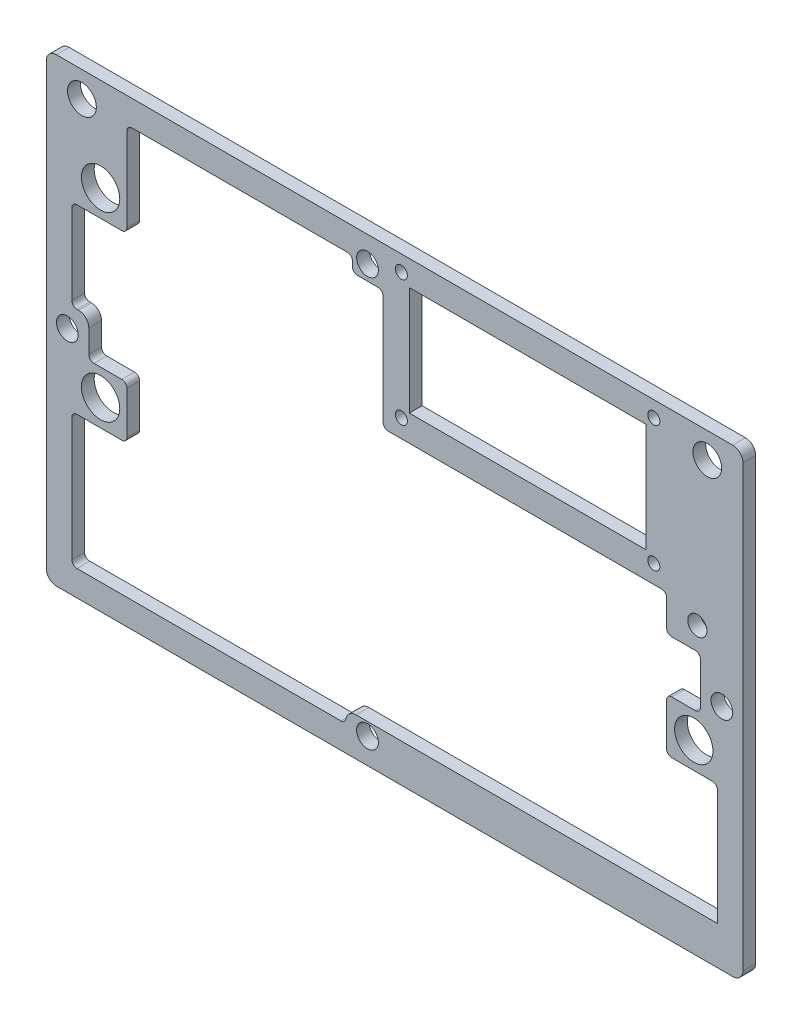
SolidWorks part; units mm, degrees
material "ABS PC"
ref_plane "Front Plane" through (0, 0, 0) normal (0, 0, 1) x (1, 0, 0)
ref_plane "Top Plane" through (0, 0, 0) normal (0, 1, 0) x (1, 0, 0)
ref_plane "Right Plane" through (0, 0, 0) normal (1, 0, 0) x (0, 0, -1)
sketch "Sketch1" plane through (0, 0, 0) normal (0, 0, 1) x (1, 0, 0)
  line L0 (94.968, 16.637) -> (-44.732, 16.637) construction
  line L1 (-61.4007, -97.663) -> (111.6368, -97.663)
  line L2 (-61.4007, -97.663) -> (-61.4007, 16.637)
  line L3 (-61.4007, 16.637) -> (111.6368, 16.637)
  line L4 (111.6368, -97.663) -> (111.6368, 16.637)
  line L5 (-61.4007, -97.663) -> (111.6368, 16.637) construction
  line L6 (-61.4007, 16.637) -> (111.6368, -97.663) construction
  point P4 (25.118, -40.513)
extrude "Boss-Extrude1" add sketch "Sketch1" along normal blind 3.175
sketch "Sketch3" plane through (0, 0, 3.175) normal (0, 0, 1) x (1, 0, 0)
  circle A0 centre (100.302, -26.543) radius 2.3813
  circle A1 centre (99.413, -51.6255) radius 4.7625
  circle A2 centre (-47.907, -51.6255) radius 4.7625
  circle A3 centre (-47.907, -6.5405) radius 4.7625
  dimension "D1" = 4.7625
  dimension "D2" = 9.525
extrude "Cut-Extrude1" cut sketch "Sketch3" against normal through all
hole_wizard "#6 Clearance Hole1" positions "Sketch5" profile "Sketch4" hole size "#6" standard "ANSI Inch" end condition through all
sketch "Sketch5" plane through (0, 0, 3.175) normal (0, 0, 1) x (1, 0, 0)
  point P0 (18.387, 10.287)
  point P3 (-56.162, -40.894)
  point P6 (106.398, -40.894)
  point P9 (18.387, -91.313)
sketch "Sketch4" plane through (18.387, 10.287, 3.175) normal (1, 0, 0) x (0, -1, 0)
  line L0 (0, 0) -> (0, 3.175)
  line L1 (0, 3.175) -> (2.1526, 3.175)
  line L2 (2.1526, 3.175) -> (2.1526, 0)
  line L5 (2.1526, 0) -> (0, 0)
  line L11 (0, -6.35) -> (0, 107.95) construction
  dimension "Thru Hole Dia." = 4.3053
  dimension "Thru Hole Depth" = 3.175
hole_wizard "#2 Clearance Hole1" positions "Sketch7" profile "Sketch6" hole size "#2" standard "ANSI Inch" end condition through all
sketch "Sketch7" plane through (0, 0, 3.175) normal (0, 0, 1) x (1, 0, 0)
  point P0 (26.788, 12.7)
  point P3 (89.488, 12.7)
  point P6 (89.488, -18.6)
  point P9 (26.788, -18.6)
sketch "Sketch6" plane through (26.788, 12.7, 3.175) normal (1, 0, 0) x (0, -1, 0)
  line L0 (0, 0) -> (0, 3.175)
  line L1 (0, 3.175) -> (1.3525, 3.175)
  line L2 (1.3525, 3.175) -> (1.3525, 0)
  line L5 (1.3525, 0) -> (0, 0)
  line L11 (0, -6.35) -> (0, 107.95) construction
  dimension "Thru Hole Dia." = 2.7051
  dimension "Thru Hole Depth" = 3.175
sketch "Sketch8" plane through (0, 0, 3.175) normal (0, 0, 1) x (1, 0, 0)
  line L9 (92.658, -23.1276) -> (22.2605, -23.1276)
  line L10 (22.2605, -23.1276) -> (22.2605, 6.5468)
  line L11 (22.2605, 6.5468) -> (14.6469, 6.5468)
  line L12 (92.658, -23.1276) -> (92.658, -32.1509)
  line L13 (28.768, 10.37) -> (28.768, -16.62)
  line L14 (28.768, -16.62) -> (87.508, -16.62)
  line L15 (87.508, -16.62) -> (87.508, 10.37)
  line L16 (87.508, 10.37) -> (28.768, 10.37)
  line L17 (28.768, 10.37) -> (28.768, -16.62)
  line L18 (28.768, -16.62) -> (87.508, -16.62)
  line L19 (87.508, -16.62) -> (87.508, 10.37)
  line L20 (87.508, 10.37) -> (28.768, 10.37)
  line L21 (92.658, -32.1509) -> (101.0704, -32.1509)
  line L22 (101.0704, -32.1509) -> (101.0704, -45.0855)
  line L23 (101.0704, -45.0855) -> (92.658, -45.0855)
  line L24 (92.658, -45.0855) -> (92.658, -58.1655)
  line L25 (92.658, -58.1655) -> (105.2868, -58.1655)
  line L26 (105.2868, -58.1655) -> (105.2868, -88.138)
  line L27 (105.2868, -88.138) -> (13.0594, -88.138)
  line L28 (13.0594, -88.138) -> (13.0594, -91.313)
  line L29 (13.0594, -91.313) -> (-55.0507, -91.313)
  line L30 (-55.0507, -91.313) -> (-55.0507, -58.1655)
  line L31 (-55.0507, -58.1655) -> (-41.367, -58.1655)
  line L32 (-41.367, -58.1655) -> (-41.367, -45.0855)
  line L33 (-41.367, -45.0855) -> (-50.8343, -45.0855)
  line L34 (-50.8343, -45.0855) -> (-50.8343, -35.5664)
  line L35 (-50.8343, -35.5664) -> (-55.0507, -35.5664)
  line L36 (-55.0507, -35.5664) -> (-55.0507, -13.0805)
  line L37 (-55.0507, -13.0805) -> (-41.367, -13.0805)
  line L38 (-41.367, -13.0805) -> (-41.367, 10.287)
  line L39 (14.6469, 6.5468) -> (14.6469, 10.287)
  line L40 (14.6469, 10.287) -> (-41.367, 10.287)
  line L43 (92.658, -45.0855) -> (109.0968, -45.0855) construction
  line L44 (111.6368, -97.663) -> (111.6368, 16.637) construction
  line L45 (-61.4007, -97.663) -> (111.6368, -97.663) construction
  line L46 (-61.4007, 16.637) -> (-61.4007, -97.663) construction
  line L47 (111.6368, 16.637) -> (-61.4007, 16.637) construction
  circle A1 centre (106.398, -40.894) radius 2.1526 construction
  circle A3 centre (18.387, -91.313) radius 2.1526 construction
  circle A8 centre (-56.162, -40.894) radius 2.1526 construction
  circle A11 centre (18.387, 10.287) radius 2.1526 construction
  circle A13 centre (26.788, -18.6) radius 1.3525 construction
  dimension "D1" = 1.27
  dimension "D10" = 1.5875
  dimension "D2" = 3.175
  dimension "D3" = 6.35
  dimension "D4" = 9.525
  dimension "D5" = 3.175
  dimension "D6" = 6.35
  dimension "D7" = 6.35
  dimension "D8" = 3.175
  dimension "D9" = 3.175
  dimension "D11" = 1.5875
  dimension "D12" = 6.35
  dimension "D13" = 3.175
  dimension "D14" = 3.175
extrude "Cut-Extrude2" cut sketch "Sketch8" against normal through all contours L19 L20 L17 L18 | L39 L40 L38 L37 L36 L35 L34 L33 L32 L31 L30 L29 L28 L27 L26 L25 L24 L23 L22 L21 L12 L9 L10 L11 region at (16.8246, -47.9652, 3.175) region at (58.138, -3.125, 3.175)
hole_wizard "#3 (0.213) Diameter Hole1" positions "3DSketch1" profile "Sketch9" hole size "#3" standard "ANSI Inch" end condition through all
sketch3d "3DSketch1"
  line L0 (18.387, 10.287, 0) -> (18.387, 10.287, 3.175) construction
  line L1 (-56.162, -40.894, 0) -> (-56.162, -40.894, 3.175) construction
  line L2 (18.387, -91.313, 0) -> (18.387, -91.313, 3.175) construction
  line L3 (106.398, -40.894, 0) -> (106.398, -40.894, 3.175) construction
  point P0 (18.387, 10.287, 3.175)
  point P5 (-56.162, -40.894, 3.175)
  point P9 (18.387, -91.313, 3.175)
  point P13 (106.398, -40.894, 3.175)
sketch "Sketch9" plane through (18.387, 10.287, 3.175) normal (1, 0, 0) x (0, -1, 0)
  line L0 (0, 0) -> (0, 3.175)
  line L1 (0, 3.175) -> (2.7051, 3.175)
  line L2 (2.7051, 3.175) -> (2.7051, 0)
  line L5 (2.7051, 0) -> (0, 0)
  line L11 (0, -6.35) -> (0, 107.95) construction
  dimension "Thru Hole Dia." = 5.4102
  dimension "Thru Hole Depth" = 3.175
hole_wizard "Ø3.0 (3) Diameter Hole1" positions "Sketch11" profile "Sketch10" hole size "Ø3.0" standard "ANSI Metric" end condition through all
sketch "Sketch11" plane through (0, 0, 3.175) normal (0, 0, 1) x (1, 0, 0)
  point P0 (26.788, 12.7)
  point P3 (89.488, 12.7)
  point P6 (89.488, -18.6)
  point P9 (26.788, -18.6)
sketch "Sketch10" plane through (26.788, 12.7, 3.175) normal (1, 0, 0) x (0, -1, 0)
  line L0 (0, 0) -> (0, 3.175)
  line L1 (0, 3.175) -> (1.5, 3.175)
  line L2 (1.5, 3.175) -> (1.5, 0)
  line L5 (1.5, 0) -> (0, 0)
  line L11 (0, -6.35) -> (0, 107.95) construction
  dimension "Thru Hole Dia." = 3
  dimension "Thru Hole Depth" = 3.175
fillet "Fillet1" radius 1.27 21 edges at (-41.367, 10.287, 1.5875) (-41.367, -13.0805, 1.5875) (-55.0507, -13.0805, 1.5875) (-55.0507, -35.5664, 1.5875) (-50.8343, -45.0855, 1.5875) (-41.367, -45.0855, 1.5875) (-41.367, -58.1655, 1.5875) (-55.0507, -58.1655, 1.5875) (-55.0507, -91.313, 1.5875) (13.0594, -91.313, 1.5875) (105.2868, -58.1655, 1.5875) (92.658, -58.1655, 1.5875) (92.658, -45.0855, 1.5875) (101.0704, -45.0855, 1.5875) (101.0704, -32.1509, 1.5875) (92.658, -32.1509, 1.5875) (92.658, -23.1276, 1.5875) (22.2605, -23.1276, 1.5875) (14.6469, 6.5468, 1.5875) (22.2605, 6.5468, 1.5875) (14.6469, 10.287, 1.5875)
fillet "Fillet2" radius 2.54 6 edges at (13.0594, -88.138, 1.5875) (-50.8343, -35.5664, 1.5875) (111.6368, 16.637, 1.5875) (111.6368, -97.663, 1.5875) (-61.4007, -97.663, 1.5875) (-61.4007, 16.637, 1.5875)
hole_wizard "1/4 Clearance Hole1" positions "Sketch12" profile "Sketch13" hole size "1/4" standard "ANSI Inch" end condition up to next
sketch "Sketch12" plane through (0, 0, 0) normal (0, 0, -1) x (-1, 0, 0)
  point P0 (-102.7785, 10.287)
  point P2 (52.5425, 10.287)
sketch "Sketch13" plane through (102.7785, 10.287, 0) normal (1, 0, 0) x (0, 1, 0)
  line L0 (0, 0) -> (0, 3.175)
  line L1 (0, 3.175) -> (3.5712, 3.175)
  line L2 (3.5712, 3.175) -> (3.5712, 0)
  line L5 (3.5712, 0) -> (0, 0)
  line L11 (0, -6.35) -> (0, 107.95) construction
  dimension "Thru Hole Dia." = 7.1425
  dimension "Thru Hole Depth" = 3.175
